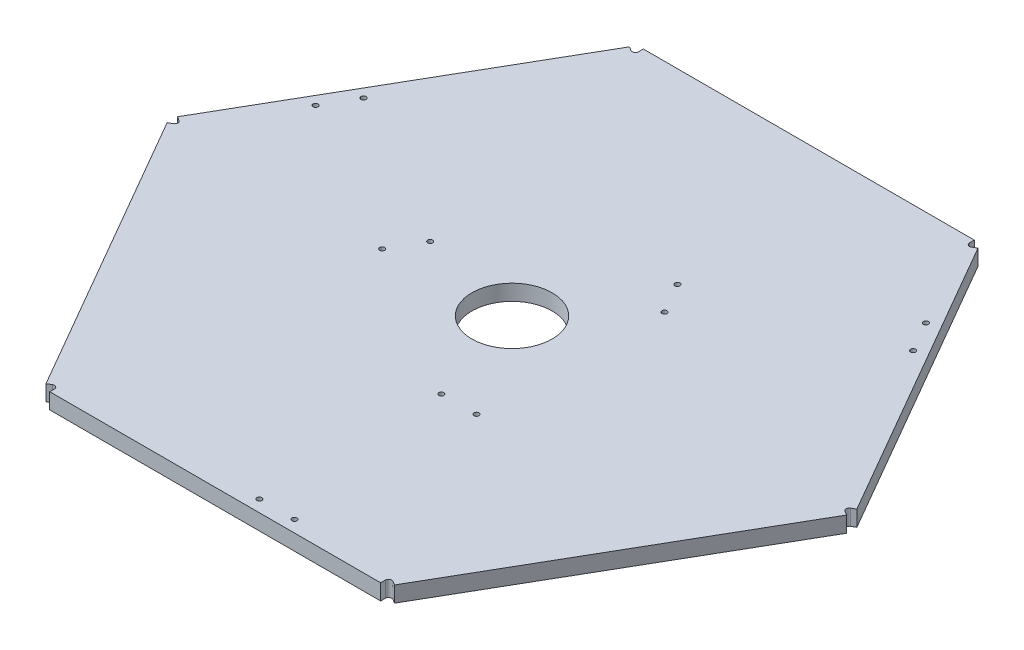
SolidWorks part; units mm, degrees
ref_plane "Front Plane" through (0, 0, 0) normal (0, 0, 1) x (1, 0, 0)
ref_plane "Top Plane" through (0, 0, 0) normal (0, 1, 0) x (1, 0, 0)
ref_plane "Right Plane" through (0, 0, 0) normal (1, 0, 0) x (0, 0, -1)
sketch "Sketch1" plane through (0, 0, 0) normal (0, 1, 0) x (1, 0, 0)
  line L1 (54.2709, 94) -> (-54.2709, 94)
  line L2 (-54.2709, 94) -> (-108.5419, 0)
  line L3 (-108.5419, 0) -> (-54.2709, -94)
  line L4 (-54.2709, -94) -> (54.2709, -94)
  line L5 (54.2709, -94) -> (108.5419, 0)
  line L6 (108.5419, 0) -> (54.2709, 94)
  circle A0 centre (0, 0) radius 94 construction
  dimension "D1" = 188
extrude "Boss-Extrude1" add sketch "Sketch1" along normal blind 5
sketch "Sketch7" plane through (0, 5, 0) normal (0, 1, 0) x (1, 0, 0)
  line L0 (54.2709, 94) -> (-54.2709, 94) construction
  line L1 (53.4049, 92.5) -> (-53.4049, 92.5) construction
  line L2 (-53.4049, 92.5) -> (-106.8098, 0) construction
  line L3 (-106.8098, 0) -> (-53.4049, -92.5) construction
  line L4 (-53.4049, -92.5) -> (53.4049, -92.5) construction
  line L5 (53.4049, -92.5) -> (106.8098, 0) construction
  line L6 (106.8098, 0) -> (53.4049, 92.5) construction
  circle A0 centre (0, 0) radius 92.5 construction
  circle A1 centre (-53.4049, 92.5) radius 1
  dimension "D2" = 2
  dimension "D1" = 185
extrude "Cut-Extrude5" cut sketch "Sketch7" against normal through all
sketch "Sketch9" plane through (0, 5, 0) normal (0, 1, 0) x (1, 0, 0)
  circle A0 centre (0, 0) radius 12.7
  dimension "D1" = 25.4
extrude "Cut-Extrude6" cut sketch "Sketch9" against normal up to next
sketch "Sketch13" plane through (0, 5, 0) normal (0, 1, 0) x (1, 0, 0)
  circle A0 centre (-88.84, 26.6245) radius 0.8
  circle A1 centre (-38.9353, -2.188) radius 0.8
  circle A2 centre (67.4775, 63.6255) radius 0.8
  circle A3 centre (21.3625, -90.25) radius 0.8
  circle A4 centre (-83.2775, 36.2591) radius 0.8
  circle A22 centre (-33.3728, 7.4466) radius 0.8
  circle A24 centre (73.04, 53.9909) radius 0.8
  circle A26 centre (17.5728, 34.813) radius 0.8
  circle A28 centre (23.1353, 25.1784) radius 0.8
  circle A38 centre (10.2375, -90.25) radius 0.8
  circle A40 centre (21.3625, -32.625) radius 0.8
  circle A42 centre (10.2375, -32.625) radius 0.8
  dimension "D1" = 1.6
extrude "Cut-Extrude7" cut sketch "Sketch13" against normal through all
sketch "Sketch17" plane through (0, 5, 0) normal (0, 1, 0) x (1, 0, 0)
  line L0 (-52.4049, 92.5) -> (-52.4049, 94)
  line L1 (54.2709, 94) -> (-54.2709, 94) construction
  line L2 (-52.4049, 94) -> (-54.2709, 94)
  line L3 (-55.2039, 92.384) -> (-53.9049, 91.634)
  line L4 (-54.2709, 94) -> (-108.5419, 0) construction
  line L5 (-55.2039, 92.384) -> (-54.2709, 94)
  circle A0 centre (-53.4049, 92.5) radius 1 construction
  arc A1 (-53.9049, 91.634) -> (-52.4049, 92.5) centre (-53.4049, 92.5) ccw
extrude "Cut-Extrude8" cut sketch "Sketch17" against normal through all
pattern_circular "CirPattern1" count 6 over 360 about axis through (0, 5, 0) along (0, 1, 0) of "Cut-Extrude5", "Cut-Extrude8"
sketch "Sketch18" plane through (0, 5, 0) normal (0, 1, 0) x (1, 0, 0)
  line L18 (-106.3098, -0.866) -> (-107.6088, -1.616)
  line L19 (-107.6088, -1.616) -> (-55.2039, -92.384)
  line L20 (-55.2039, -92.384) -> (-53.9049, -91.634)
  line L21 (-52.4049, -92.5) -> (-52.4049, -94)
  line L22 (-52.4049, -94) -> (52.4049, -94)
  line L23 (52.4049, -94) -> (52.4049, -92.5)
  line L24 (53.9049, -91.634) -> (55.2039, -92.384)
  line L25 (55.2039, -92.384) -> (107.6088, -1.616)
  line L26 (107.6088, -1.616) -> (106.3098, -0.866)
  line L27 (106.3098, 0.866) -> (107.6088, 1.616)
  line L28 (107.6088, 1.616) -> (55.2039, 92.384)
  line L29 (55.2039, 92.384) -> (53.9049, 91.634)
  line L30 (52.4049, 92.5) -> (52.4049, 94)
  line L31 (52.4049, 94) -> (-52.4049, 94)
  line L32 (-52.4049, 94) -> (-52.4049, 92.5)
  line L33 (-53.9049, 91.634) -> (-55.2039, 92.384)
  line L34 (-55.2039, 92.384) -> (-107.6088, 1.616)
  line L35 (-107.6088, 1.616) -> (-106.3098, 0.866)
  line L36 (-106.3098, -0.866) -> (-107.6088, -1.616)
  line L37 (-107.6088, -1.616) -> (-55.2039, -92.384)
  line L38 (-55.2039, -92.384) -> (-53.9049, -91.634)
  line L39 (-52.4049, -92.5) -> (-52.4049, -94)
  line L40 (-52.4049, -94) -> (52.4049, -94)
  line L41 (52.4049, -94) -> (52.4049, -92.5)
  line L42 (53.9049, -91.634) -> (55.2039, -92.384)
  line L43 (55.2039, -92.384) -> (107.6088, -1.616)
  line L44 (107.6088, -1.616) -> (106.3098, -0.866)
  line L45 (106.3098, 0.866) -> (107.6088, 1.616)
  line L46 (107.6088, 1.616) -> (55.2039, 92.384)
  line L47 (55.2039, 92.384) -> (53.9049, 91.634)
  line L48 (52.4049, 92.5) -> (52.4049, 94)
  line L49 (52.4049, 94) -> (-52.4049, 94)
  line L50 (-52.4049, 94) -> (-52.4049, 92.5)
  line L51 (-53.9049, 91.634) -> (-55.2039, 92.384)
  line L52 (-55.2039, 92.384) -> (-107.6088, 1.616)
  line L53 (-107.6088, 1.616) -> (-106.3098, 0.866)
  arc A6 (-52.4049, -92.5) -> (-53.9049, -91.634) centre (-53.4049, -92.5) ccw
  arc A7 (53.9049, -91.634) -> (52.4049, -92.5) centre (53.4049, -92.5) ccw
  arc A8 (106.3098, 0.866) -> (106.3098, -0.866) centre (106.8098, 0) ccw
  arc A9 (52.4049, 92.5) -> (53.9049, 91.634) centre (53.4049, 92.5) ccw
  arc A10 (-53.9049, 91.634) -> (-52.4049, 92.5) centre (-53.4049, 92.5) ccw
  arc A11 (-106.3098, -0.866) -> (-106.3098, 0.866) centre (-106.8098, 0) ccw
  arc A12 (-52.4049, -92.5) -> (-53.9049, -91.634) centre (-53.4049, -92.5) ccw
  arc A13 (53.9049, -91.634) -> (52.4049, -92.5) centre (53.4049, -92.5) ccw
  arc A14 (106.3098, 0.866) -> (106.3098, -0.866) centre (106.8098, 0) ccw
  arc A15 (52.4049, 92.5) -> (53.9049, 91.634) centre (53.4049, 92.5) ccw
  arc A16 (-53.9049, 91.634) -> (-52.4049, 92.5) centre (-53.4049, 92.5) ccw
  arc A17 (-106.3098, -0.866) -> (-106.3098, 0.866) centre (-106.8098, 0) ccw
  dimension "D1" = 0
